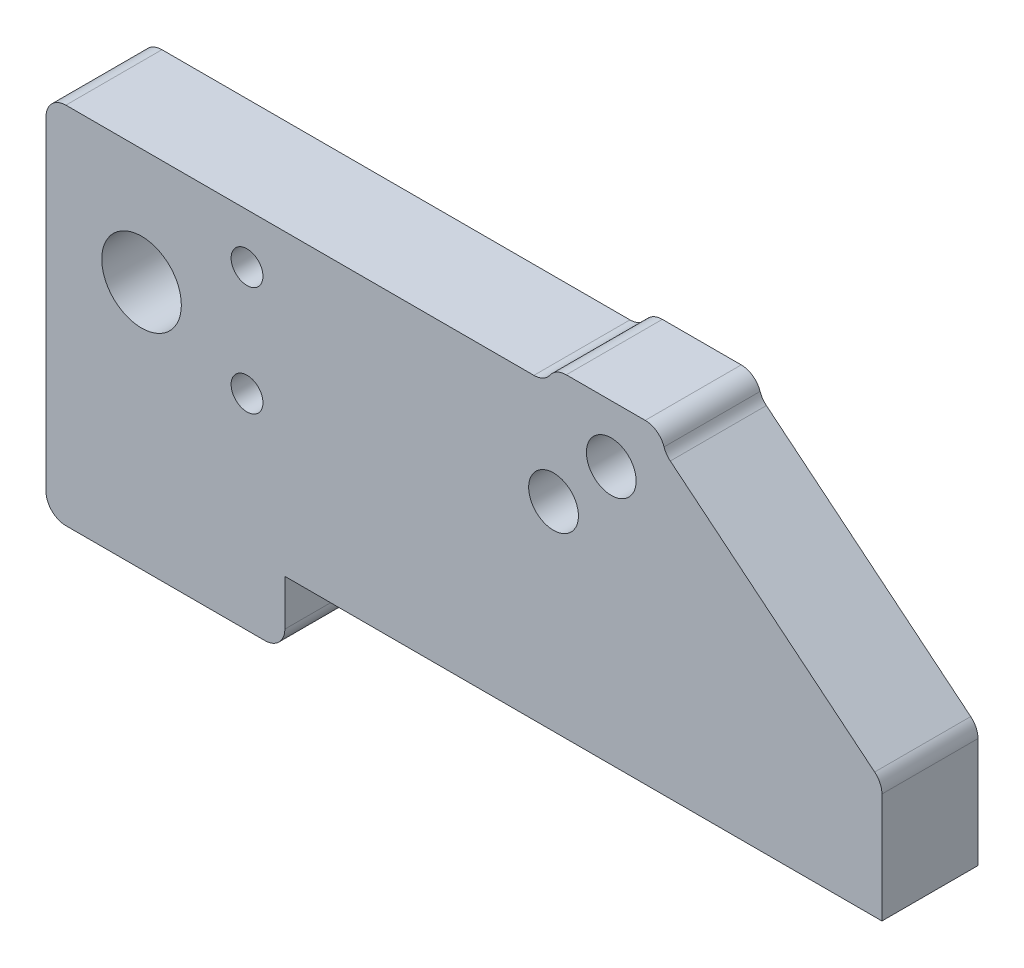
SolidWorks part; units mm, degrees
material "6061-T4 (SS)"
ref_plane "Front" through (0, 0, 0) normal (0, 0, 1) x (1, 0, 0)
ref_plane "Top" through (0, 0, 0) normal (0, 1, 0) x (1, 0, 0)
ref_plane "Right" through (0, 0, 0) normal (1, 0, 0) x (0, 0, -1)
sketch "Sketch1" plane through (0, 0, 0) normal (0, 0, 1) x (1, 0, 0)
  line L0 (-5.5, 10) -> (-5.5, 15) construction
  line L1 (0, 0) -> (-11, 0)
  line L2 (0, 0) -> (0, 15) construction
  line L4 (-11, 0) -> (-11, 15)
  line L5 (-5.5, 10) -> (-11, 10) construction
  line L6 (-5.5, 10) -> (0, 10) construction
  line L7 (0, 15) -> (11, 6)
  line L8 (11, 6) -> (11, 0)
  line L9 (11, 0) -> (0, 0)
  line L10 (-11, 0) -> (-19, 0)
  line L11 (-19, 0) -> (-19, -3.3)
  line L12 (-19, -3.3) -> (-31, -3.3)
  line L13 (-31, -3.3) -> (-31, 15)
  line L14 (-31, 15) -> (-11, 15)
  line L15 (0, 15) -> (0, 15.8373)
  line L16 (-31, 15) -> (-19, 15)
  line L17 (-31, 15) -> (-31, 17)
  line L20 (0, 15.8373) -> (-5.5, 15.8373)
  line L22 (-5.5, 15.8373) -> (-5.5, 15)
  line L23 (-5.5, 15) -> (-11, 15)
  circle A0 centre (-26.2, 9.2) radius 2
  dimension "D3" = 10
  dimension "D12" = 4
  dimension "D2" = 15
  dimension "D4" = 6
  dimension "D5" = 22
  dimension "D6" = 8
  dimension "D7" = 12
  dimension "D8" = 3.3
  dimension "D10" = 12.5
  dimension "D11" = 4.8
  dimension "D14" = 5.5
extrude "Boss-Extrude1" add sketch "Sketch1" along normal blind 4.826 contours L9 L8 L7 L4 L1 region at (-1.3176, 6.8466, 0)
sketch "Sketch_baseplate_mounting" plane through (0, 0, 0) normal (0, -1, 0) x (-1, 0, 0)
  line L0 (11, -4.826) -> (11, 0) construction
  line L1 (4, -2.413) -> (11, -2.413) construction
  line L2 (-11, -2.413) -> (-8, -2.413) construction
  line L4 (-11, -4.826) -> (-11, 0) construction
  dimension "D1" = 7
  dimension "D2" = 3
hole_wizard "M3x0.5 Tapped Hole1" positions "Sketch8" profile "Sketch10" tap size "M3x0.5" standard "ANSI Metric" end condition through all
sketch "Sketch8" plane through (0, 0, 4.826) normal (0, 0, 1) x (1, 0, 0)
  point P0 (-5.5, 10)
sketch "Sketch10" plane through (-5.5, 10, 4.826) normal (1, 0, 0) x (0, -1, 0)
  line L0 (0, 0) -> (0, 4.826)
  line L1 (0, 4.826) -> (1.25, 4.826)
  line L2 (1.25, 4.826) -> (1.25, 0)
  line L5 (1.25, 0) -> (0, 0)
  line L11 (0, -6.35) -> (0, 107.95) construction
  dimension "Thread Major Dia." = 2.5
  dimension "Thru Tap Drill Depth" = 4.826
hole_wizard "Tap Drill for M3x0.5 Tap1" positions "3DSketch1" profile "Sketch5" hole size "M3x0.5" standard "ANSI Metric"
sketch3d "3DSketch1"
  point P0 (-4, 0, 2.413)
  point P3 (8, 0, 2.413)
sketch "Sketch5" plane through (-4, 0, 2.413) normal (1, 0, 0) x (0, 0, -1)
  line L0 (0, 0) -> (0, 5.7511)
  line L1 (0, 5.7511) -> (1.25, 5)
  line L2 (1.25, 5) -> (1.25, 0)
  line L5 (1.25, 0) -> (0, 0)
  line L10 (0, 5.7511) -> (-1.25, 5) construction
  line L11 (0, -6.35) -> (0, 107.95) construction
  dimension "Hole Dia." = 2.5
  dimension "Hole Depth" = 5
  dimension "Drill Angle" = 118
sketch "Sketch_chipper_mounting" plane through (0, 0, 4.826) normal (0, 0, 1) x (1, 0, 0)
  line L0 (4.5, 0) -> (4.5, 4.5) construction
  line L1 (11, 0) -> (-11, 0) construction
  circle A1 centre (-5.5, 10) radius 1.25 construction
  dimension "D1" = 4.5
  dimension "D2" = 10
hole_wizard "M3x0.5 Tapped Hole2" positions "3DSketch2" profile "Sketch7" tap size "M3x0.5" standard "ANSI Metric" end condition through all
sketch3d "3DSketch2"
  point P6 (-2.6, 12.97, 0)
  point P9 (0, 0, 0)
sketch "Sketch7" plane through (-2.6, 12.97, 0) normal (1, 0, 0) x (0, 1, 0)
  line L0 (0, 0) -> (0, 4.826)
  line L1 (0, 4.826) -> (1.25, 4.826)
  line L2 (1.25, 4.826) -> (1.25, 0)
  line L5 (1.25, 0) -> (0, 0)
  line L11 (0, -6.35) -> (0, 107.95) construction
  dimension "Thru Tap Drill Dia." = 2.5
  dimension "Thru Tap Drill Depth" = 4.826
extrude "Boss-Extrude2" add sketch "Sketch1<3>" along normal up to surface (4.826 mm away) contours L14 L13 L12 L11 L10 L4 region at (-21.2845, 6.3267, 0) up to face at (-3.85, 12.97, 4.826)
sketch "Sketch1<3>" plane through (0, 0, 0) normal (0, 0, 1) x (1, 0, 0) same geometry as "Sketch1"
fillet "Fillet1" radius 1 6 edges at (-31, 15, 2.413) (-19, -3.3, 2.413) (-31, -3.3, 2.413) (11, 6, 2.413) (-5.5, 15, 2.413) (0, 15, 2.413)
hole_wizard "M1 Tapped Holes" positions "Sketch11" profile "Sketch12" legacy
sketch "Sketch11" plane through (0, 0, 4.826) normal (0, 0, 1) x (1, 0, 0)
  line L0 (-19, 7) -> (-20.9, 7) construction
  line L2 (-20.9, 7) -> (-20.9, -3.3) construction
  line L5 (-20.9, 7) -> (-20.9, 12.5) construction
  line L7 (-27.25, 12.5) -> (-14.55, 12.5) construction
  line L8 (-20, -3.3) -> (-30, -3.3) construction
  point P0 (-20.9, 12.5)
  point P2 (-20.9, 7)
  dimension "D1" = 10.3
  dimension "D2" = 1.9
  dimension "D3" = 12.7
  dimension "D4" = 15.8
sketch "Sketch12" plane through (-20.9, 12.5, 4.826) normal (1, 0, 0) x (0, -1, 0)
  line L0 (0, 0) -> (0, 4.825)
  line L1 (0, 4.825) -> (0.8, 4.825)
  line L2 (0.8, 4.825) -> (0.8, 0)
  line L3 (0.8, 0) -> (0, 0)
  line L4 (0, 110) -> (0, -10) construction
  dimension "Diameter" = 1.6
  dimension "Depth" = 4.825
fillet "Fillet2" radius 1 2 edges at (0, 15.8373, 2.413) (-5.5, 15.8373, 2.413)
